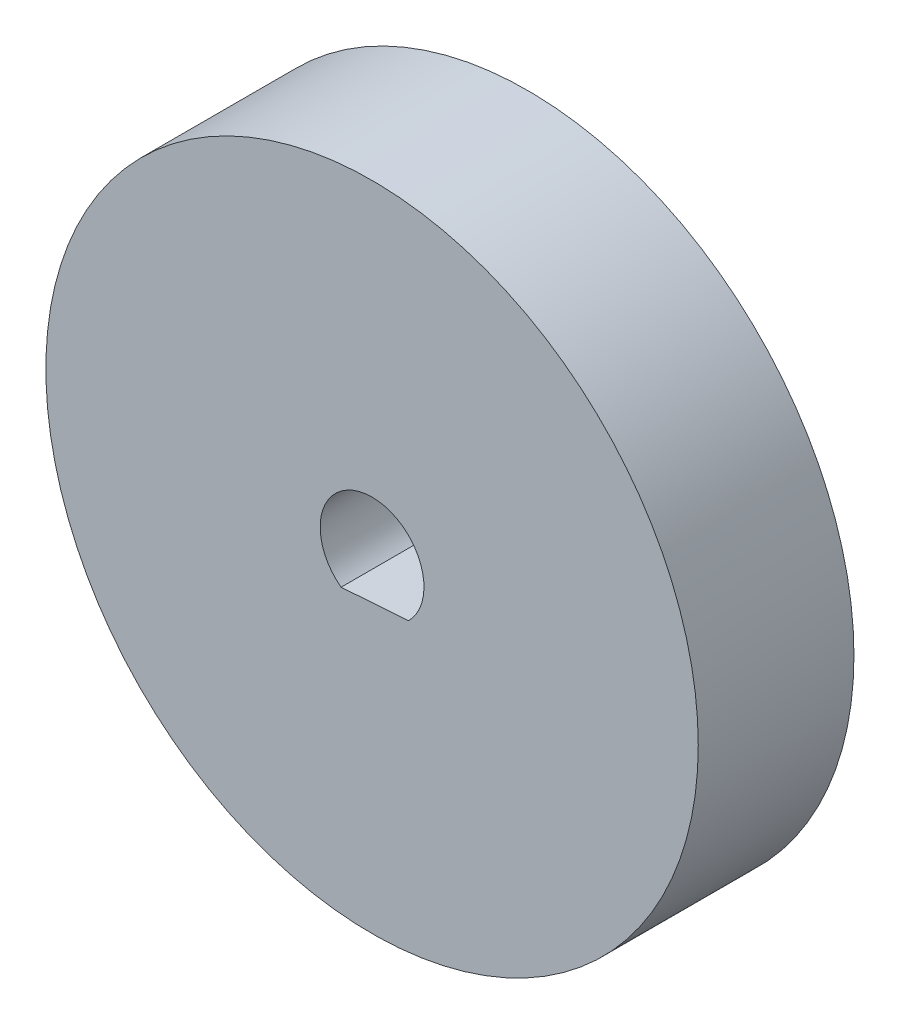
SolidWorks part; units mm, degrees
ref_plane "Front Plane" through (0, 0, 0) normal (0, 0, 1) x (1, 0, 0)
ref_plane "Top Plane" through (0, 0, 0) normal (0, 1, 0) x (1, 0, 0)
ref_plane "Right Plane" through (0, 0, 0) normal (1, 0, 0) x (0, 0, -1)
sketch "Sketch1" plane through (0, 0, 0) normal (0, 0, 1) x (1, 0, 0)
  circle A0 centre (0, 7.2896) radius 11.176
  dimension "D1" = 22.352
extrude "Boss-Extrude1" add sketch "Sketch1" along normal blind 5.334
sketch "Sketch2" plane through (0, 0, 0) normal (0, 0, -1) x (-1, 0, 0)
  line L1 (-1.2473, 6.0225) -> (1.0613, 5.8631)
  circle A0 centre (0, 7.2896) radius 1.778
  circle A1 centre (0, 7.2896) radius 11.176 construction
  dimension "D1" = 3.556
  dimension "D3" = 0
  dimension "D2" = 1.35
extrude "Cut-Extrude1" cut sketch "Sketch2" against normal through all contours L1 A0 region at (-0.0077, 7.4009, 0)
equation "\"MDF\"= .21in"
equation "\"Foamcore\"= .13in"
equation "\"Gmaterial\"= \"MDF\""
equation "\"D1@Boss-Extrude1\"=\"MDF\""
